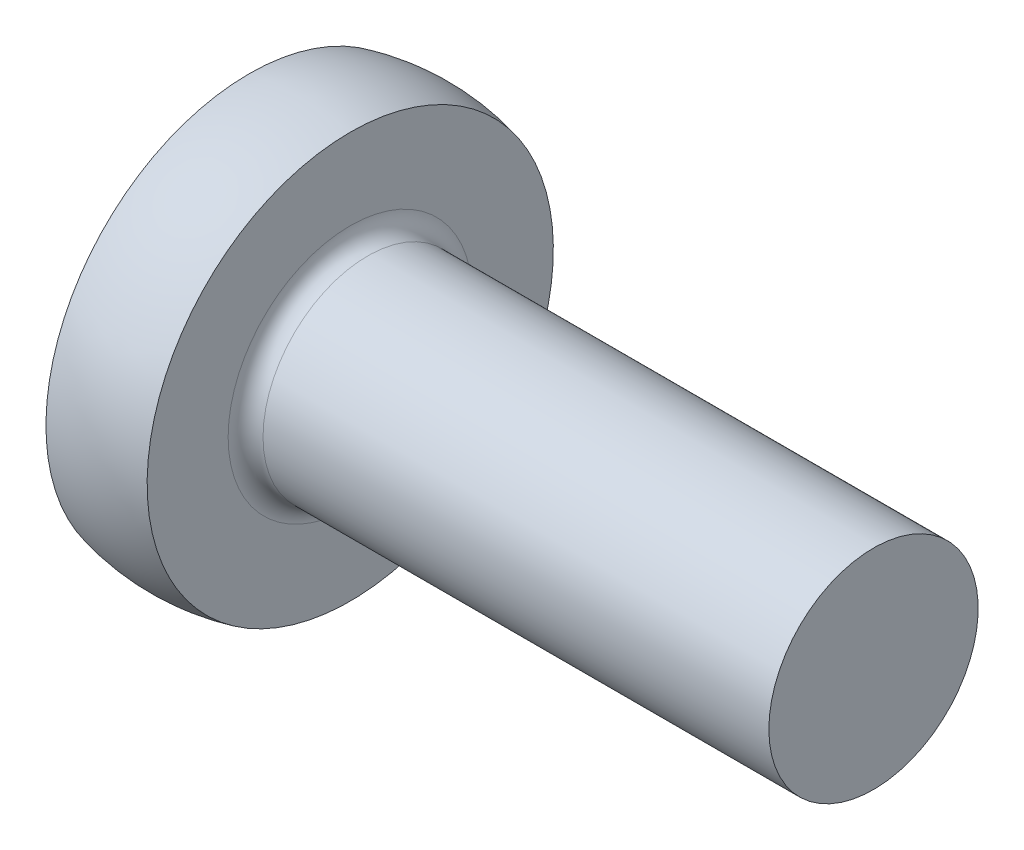
SolidWorks part; units mm, degrees
ref_plane "Front" through (0, 0, 0) normal (0, 0, 1) x (1, 0, 0)
ref_plane "Top" through (0, 0, 0) normal (0, 1, 0) x (1, 0, 0)
ref_plane "Right" through (0, 0, 0) normal (1, 0, 0) x (0, 0, -1)
sketch "Sketch1" plane through (0, 0, 0) normal (0, 0, 1) x (1, 0, 0)
  line L0 (0, 1.1644) -> (0, 0)
  line L1 (0.58, 1.1644) -> (0.58, 0.6)
  line L2 (0, 0) -> (3.58, 0)
  line L3 (3.58, 0) -> (3.58, 0.6)
  line L4 (3.58, 0.6) -> (0.58, 0.6)
  line L5 (-2.3183, 0) -> (6.9456, 0) construction
  arc A0 (0.58, 1.1644) -> (0, 1.1644) centre (0.29, 0) ccw
  dimension "D3" = 0.29
revolve "Base-Revolve" add sketch "Sketch1" angle 360 about L5
fillet "Fillet1" radius 0.1 1 edges at (0.58, 0, 0.6)
equation "\"D3@Sketch1\" = \"K@Sketch1\" / 2"
